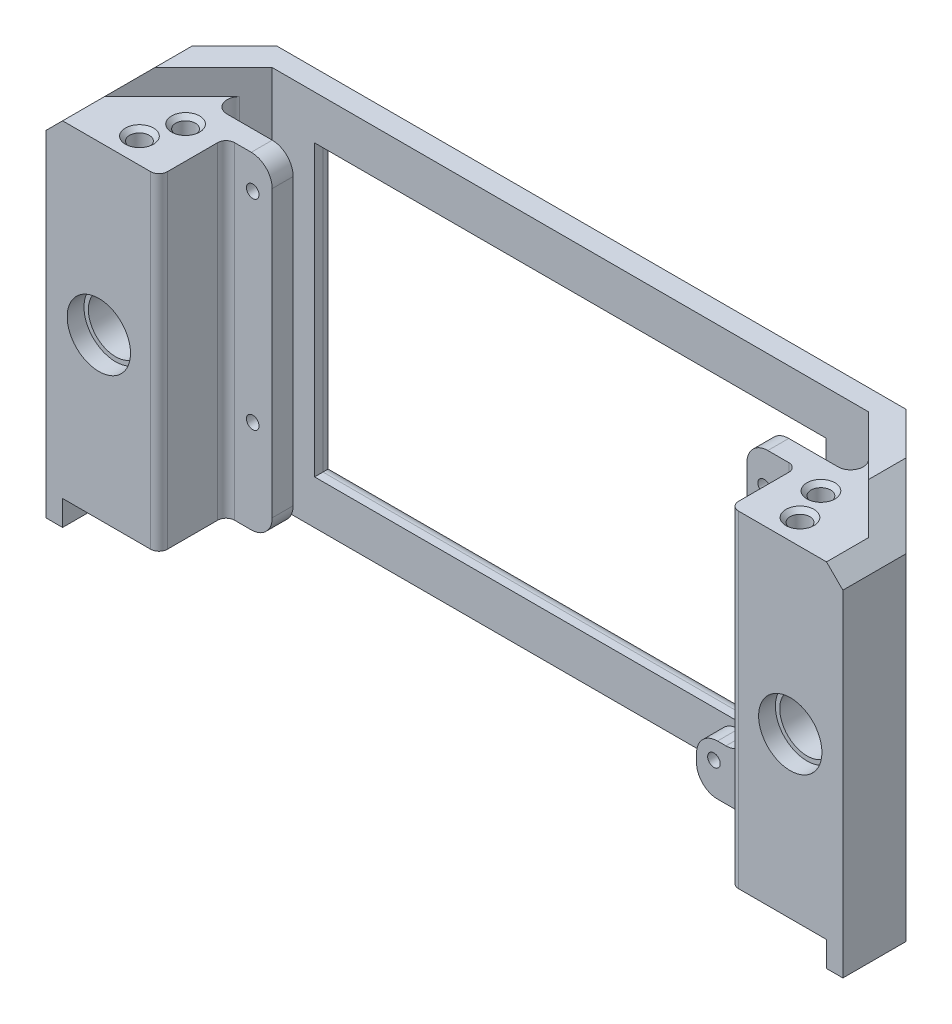
SolidWorks part; units mm, degrees
ref_plane "Front Plane" through (0, 0, 0) normal (0, 0, 1) x (1, 0, 0)
ref_plane "Top Plane" through (0, 0, 0) normal (0, 1, 0) x (1, 0, 0)
ref_plane "Right Plane" through (0, 0, 0) normal (1, 0, 0) x (0, 0, -1)
sketch "Sketch1" plane through (0, 0, 0) normal (0, 0, 1) x (1, 0, 0)
  line L1 (-95, 45) -> (95, 45)
  line L2 (-95, 45) -> (-95, -45)
  line L3 (-95, -45) -> (95, -45)
  line L4 (95, 45) -> (95, -45)
  line L5 (-95, 45) -> (95, -45) construction
  line L6 (-95, -45) -> (95, 45) construction
  line L7 (-61, 34.5) -> (61, 34.5)
  line L8 (-61, 34.5) -> (-61, -34.5)
  line L9 (-61, -34.5) -> (61, -34.5)
  line L10 (61, 34.5) -> (61, -34.5)
  line L11 (-61, 34.5) -> (61, -34.5) construction
  line L12 (-61, -34.5) -> (61, 34.5) construction
  point P0 (0, 0)
  point P6 (0, 0)
  dimension "D1" = 122
  dimension "D2" = 190
  dimension "D3" = 69
  dimension "D4" = 90
extrude "Boss-Extrude1" add sketch "Sketch1" along normal blind 5
sketch "Sketch2" plane through (0, 0, 5) normal (0, 0, 1) x (1, 0, 0)
  line L0 (-95, -45) -> (95, -45) construction
  line L1 (-95, 45) -> (-91.1, 45)
  line L2 (-95, 45) -> (-95, -45)
  line L3 (-95, -45) -> (-91.1, -45)
  line L4 (-91.1, 45) -> (-91.1, -45)
  line L5 (0, 0) -> (0, 45) construction
  line L6 (95, 45) -> (-95, 45) construction
  line L7 (95, -45) -> (91.1, -45)
  line L8 (91.1, 45) -> (91.1, -45)
  line L9 (95, 45) -> (91.1, 45)
  line L10 (95, 45) -> (95, -45)
  dimension "D1" = 3.9
extrude "Boss-Extrude2" add sketch "Sketch2" along normal blind 30
sketch "Sketch3" plane through (0, 45, 0) normal (0, 1, 0) x (1, 0, 0)
  line L0 (-91.1, -35) -> (-91.1, -5) construction
  line L1 (-91.1, -14) -> (-57.1, -14)
  line L2 (-91.1, -14) -> (-91.1, -19)
  line L3 (-91.1, -19) -> (-57.1, -19)
  line L4 (-57.1, -14) -> (-57.1, -19)
  line L5 (91.1, -35) -> (91.1, -5) construction
  line L6 (91.1, -14) -> (44.1, -14)
  line L7 (91.1, -14) -> (91.1, -19)
  line L8 (91.1, -19) -> (44.1, -19)
  line L9 (44.1, -14) -> (44.1, -19)
  line L10 (91.1, -5) -> (-91.1, -5) construction
  dimension "D1" = 9
  dimension "D2" = 9
  dimension "D3" = 5
  dimension "D4" = 5
  dimension "D5" = 34
  dimension "D6" = 47
extrude "Boss-Extrude3" add sketch "Sketch3" against normal up to surface (90 mm away) up to face at (0, -45, 18.75)
sketch "Sketch4" plane through (0, 0, 19) normal (0, 0, 1) x (1, 0, 0)
  line L0 (91.1, -45) -> (91.1, 45) construction
  line L1 (-91.1, 45) -> (91.1, 45)
  line L2 (-91.1, 45) -> (-91.1, 39)
  line L3 (-91.1, 39) -> (91.1, 39)
  line L4 (91.1, 45) -> (91.1, 39)
  line L5 (0, 0) -> (-91.1, 0) construction
  line L6 (-91.1, -45) -> (-91.1, 45) construction
  line L7 (-91.1, -39) -> (91.1, -39)
  line L8 (91.1, -45) -> (91.1, -39)
  line L9 (-91.1, -45) -> (91.1, -45)
  line L10 (-91.1, -45) -> (-91.1, -39)
  dimension "D1" = 6
extrude "Cut-Extrude1" cut sketch "Sketch4" against normal blind 5
sketch "Sketch5" plane through (0, 0, 19) normal (0, 0, 1) x (1, 0, 0)
  line L0 (0, 0) -> (-61.75, 0) construction
  line L1 (-70.2, 37.38) -> (70.2, 37.38) construction
  line L2 (-70.2, 37.38) -> (-70.2, -37.38) construction
  line L3 (-70.2, -37.38) -> (70.2, -37.38) construction
  line L4 (70.2, 37.38) -> (70.2, -37.38) construction
  line L5 (-70.2, 37.38) -> (70.2, -37.38) construction
  line L6 (-70.2, -37.38) -> (70.2, 37.38) construction
  line L7 (-61.75, 0) -> (-61.75, 31.13) construction
  line L8 (-61.75, 0) -> (-61.75, -16.61) construction
  line L9 (48.25, 0) -> (60.23, 0) construction
  line L10 (60.23, 0) -> (60.23, 31.13) construction
  line L11 (0, 0) -> (48.25, 0) construction
  line L12 (48.25, 0) -> (48.25, -31.38) construction
  circle A0 centre (-61.75, 31.13) radius 1.5
  circle A1 centre (-61.75, -16.61) radius 1.5
  circle A2 centre (60.23, 31.13) radius 1.5
  circle A3 centre (48.25, -31.38) radius 1.5
  point P0 (0, 0)
  dimension "D10" = 3
  dimension "D11" = 3
  dimension "D12" = 3
  dimension "D13" = 3
  dimension "D1" = 140.4
  dimension "D2" = 74.76
  dimension "D3" = 61.75
  dimension "D4" = 31.13
  dimension "D5" = 16.61
  dimension "D6" = 60.23
  dimension "D7" = 31.13
  dimension "D8" = 48.25
  dimension "D9" = 31.38
extrude "Cut-Extrude2" cut sketch "Sketch5" against normal up to surface (5 mm away) up to face at (67.6, 0, 14)
sketch "Sketch6" plane through (0, 0, 19) normal (0, 0, 1) x (1, 0, 0)
  line L1 (44.1, 39) -> (56.1, 39)
  line L2 (44.1, 39) -> (44.1, -27)
  line L3 (44.1, -27) -> (56.1, -27)
  line L4 (56.1, 39) -> (56.1, -27)
  dimension "D1" = 12
  dimension "D2" = 66
extrude "Cut-Extrude3" cut sketch "Sketch6" against normal up to surface (5 mm away) up to face at (46.75, -31.38, 14)
fillet "Fillet3" radius 3 4 edges at (-61, 0, 0) (0, -34.5, 0) (61, 0, 0) (0, 34.5, 0)
chamfer "Chamfer6" distance 20 angle 45 4 edges at (91.1, 0, 5) (95, 0, 0) (-95, 0, 0) (-91.1, 0, 5)
sketch "Sketch7" plane through (0, 39, 0) normal (0, 1, 0) x (1, 0, 0)
  line L0 (-85.1, -19) -> (-91.1, -25)
  line L1 (-91.1, -25) -> (-91.1, -35)
  line L2 (-91.1, -35) -> (-68.1, -35)
  line L3 (-68.1, -35) -> (-68.1, -19)
  line L4 (-85.1, -19) -> (-57.1, -19) construction
  line L5 (-68.1, -19) -> (-85.1, -19)
  line L6 (0, 0) -> (0, -5) construction
  line L7 (71.1, -5) -> (-71.1, -5) construction
  line L8 (68.1, -35) -> (68.1, -19)
  line L9 (91.1, -35) -> (68.1, -35)
  line L10 (91.1, -25) -> (91.1, -35)
  line L11 (85.1, -19) -> (91.1, -25)
  line L12 (68.1, -19) -> (85.1, -19)
  dimension "D1" = 23
extrude "Boss-Extrude4" add sketch "Sketch7" against normal up to surface (78 mm away) up to face at (-69.85, -39, 16.5)
fillet "Fillet4" radius 5 6 edges at (-57.1, -39, 16.5) (-57.1, 39, 16.5) (56.1, 39, 16.5) (44.1, -39, 16.5) (44.1, -27, 16.5) (56.1, -27, 16.5)
fillet "Fillet5" radius 2 4 edges at (-68.1, 0, 35) (68.1, 0, 35) (68.1, 0, 19) (-68.1, 0, 19)
fillet "Fillet6" radius 3 2 edges at (-80.1, 0, 14) (80.1, 0, 14)
sketch "Sketch9" plane through (0, 0, 35) normal (0, 0, 1) x (1, 0, 0)
  line L6 (0, 0) -> (0, -45) construction
  line L7 (-71.1, -45) -> (71.1, -45) construction
  line L8 (-95, 45) -> (-95, -45) construction
  line L9 (-95, 39) -> (-82.45, 39) construction
  line L10 (-95, 39) -> (-95, -0.9074) construction
  line L11 (-95, -0.9074) -> (-82.45, -0.9074) construction
  line L12 (-82.45, 39) -> (-82.45, -0.9074) construction
  line L13 (-91.1, 39) -> (-70.1, 39) construction
  circle A0 centre (-82.45, -0.9074) radius 6.5
  circle A1 centre (82.45, -0.9074) radius 6.5
  dimension "D3" = 13
  dimension "D1" = 39.9074
  dimension "D2" = 12.55
extrude "Cut-Extrude4" cut sketch "Sketch9" against normal blind 10
sketch "Sketch10" plane through (0, 0, 35) normal (0, 0, 1) x (1, 0, 0)
  circle A0 centre (-82.45, -0.9074) radius 7.55
  circle A1 centre (82.45, -0.9074) radius 7.55
  dimension "D1" = 15.1
  dimension "D2" = 15.1
extrude "Cut-Extrude5" cut sketch "Sketch10" against normal blind 4
sketch "Sketch12" plane through (-68.1, 0, 0) normal (1, 0, 0) x (0, 0, -1)
  line L0 (-33, -4.4074) -> (-29, -4.4074)
  line L1 (-33, 39) -> (-23, 39) construction
  line L2 (-33, 39) -> (-33, -0.9074) construction
  line L3 (-33, -0.9074) -> (-23, -0.9074) construction
  line L4 (-23, 39) -> (-23, -0.9074) construction
  line L5 (-33, 6.5926) -> (-23, 6.5926) construction
  line L6 (-33, 6.5926) -> (-33, -8.4074) construction
  line L7 (-33, -8.4074) -> (-23, -8.4074) construction
  line L8 (-23, 6.5926) -> (-23, -8.4074) construction
  line L9 (-33, 6.5926) -> (-23, -8.4074) construction
  line L10 (-33, -8.4074) -> (-23, 6.5926) construction
  line L11 (-33, 6.5926) -> (-29, 6.5926)
  line L12 (-33, 6.5926) -> (-33, 2.5926)
  line L13 (-33, 2.5926) -> (-29, 2.5926)
  line L14 (-29, 6.5926) -> (-29, 2.5926)
  line L15 (-29, -8.4074) -> (-29, -4.4074)
  line L16 (-33, -8.4074) -> (-29, -8.4074)
  line L17 (-33, -8.4074) -> (-33, -4.4074)
  point P5 (-28, -0.9074)
  dimension "D1" = 39.9074
  dimension "D2" = 10
  dimension "D3" = 15
  dimension "D4" = 10
  dimension "D5" = 4
  dimension "D6" = 4
sketch "Sketch15" plane through (0, 39, 0) normal (0, 1, 0) x (1, 0, 0)
  line L0 (68.1, -21) -> (68.1, -33) construction
  line L5 (72.8574, -14) -> (61.1, -14) construction
  line L6 (91.1, -35) -> (68.1, -35) construction
  line L7 (91.1, -35) -> (91.1, -14) construction
  line L8 (91.1, -14) -> (68.1, -14) construction
  line L9 (68.1, -35) -> (68.1, -14) construction
  line L10 (68.1, -14) -> (75.7667, -21) construction
  line L11 (75.7667, -21) -> (83.4333, -28) construction
  line L12 (83.4333, -28) -> (91.1, -35) construction
  line L13 (0, 0) -> (0, -5) construction
  line L14 (71.1, -5) -> (-71.1, -5) construction
  line L15 (75.7667, -21) -> (75.7667, -29) construction
  line L16 (75.7667, -29) -> (78.7667, -29) construction
  circle A0 centre (75.7667, -21) radius 2.35
  circle A1 centre (83.4333, -28) radius 2.35 construction
  circle A2 centre (-75.7667, -21) radius 2.35
  circle A3 centre (-83.4333, -28) radius 2.35 construction
  circle A6 centre (78.7667, -29) radius 2.35
  circle A7 centre (-78.7667, -29) radius 2.35
  dimension "D1" = 4.7
  dimension "D2" = 4.7
  dimension "D6" = 3
  dimension "D7" = 4.7
  dimension "D3" = 23
  dimension "D4" = 21
  dimension "D5" = 8
extrude "Cut-Extrude7" cut sketch "Sketch15" against normal blind 8
chamfer "Chamfer7" distance 1 angle 45 4 edges at (-75.7667, 39, 18.65) (75.7667, 39, 23.35) (-78.7667, 39, 26.65) (78.7667, 39, 31.35)
sketch "Sketch17" plane through (0, -39, 0) normal (0, -1, 0) x (1, 0, 0)
  line L0 (0, 0) -> (0, 5) construction
  line L1 (91.1, 35) -> (68.1, 35) construction
  line L2 (91.1, 35) -> (91.1, 19) construction
  line L3 (91.1, 19) -> (68.1, 19) construction
  line L4 (68.1, 35) -> (68.1, 19) construction
  line L5 (-71.1, 5) -> (71.1, 5) construction
  line L6 (68.1, 33) -> (68.1, 21) construction
  line L7 (66.1, 19) -> (49.1, 19) construction
  circle A0 centre (79.6, 27) radius 6.1
  circle A1 centre (-79.6, 27) radius 6.1
  dimension "D2" = 12.2
  dimension "D1" = 11.5
  dimension "D3" = 8
extrude "Cut-Extrude8" cut sketch "Sketch17" against normal blind 3.2
fillet "Fillet7" radius 0.2 2 edges at (-85.7, -39, 27) (85.7, -39, 27)
chamfer "Chamfer8" distance 9.9 angle 45 2 edges at (-95, 45, 27.5) (95, 45, 27.5)
